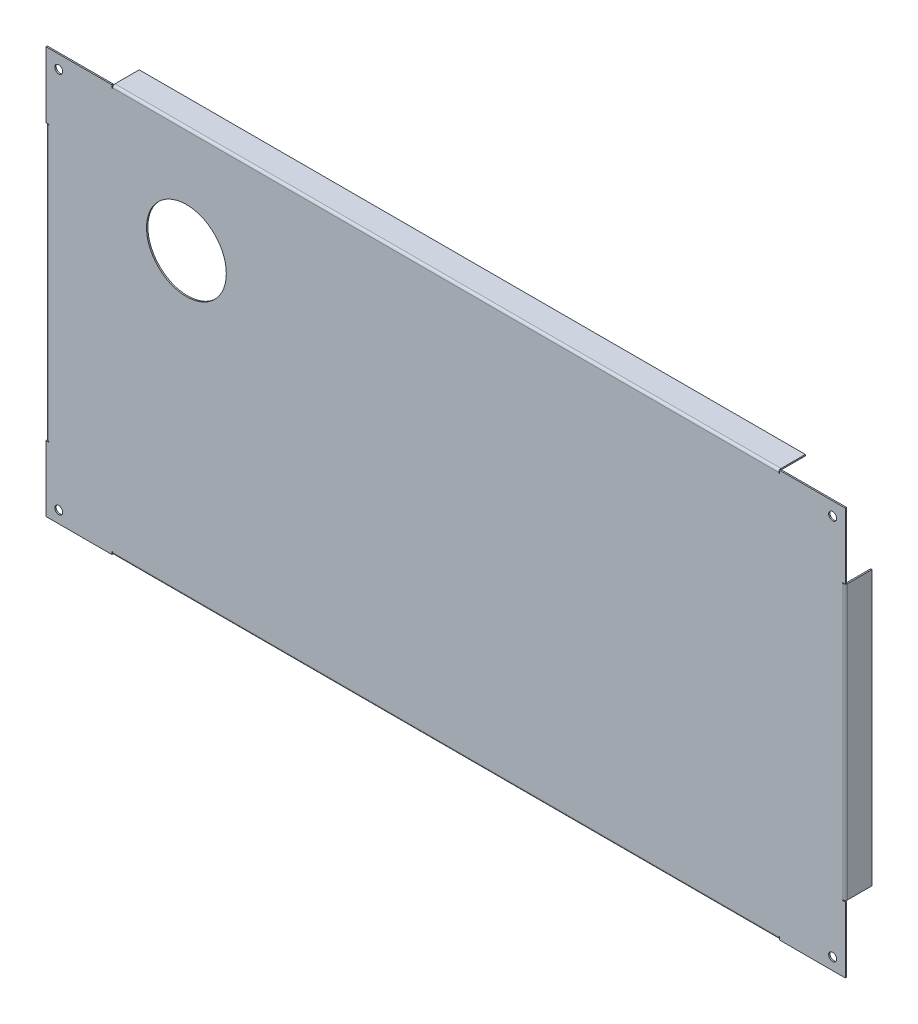
SolidWorks part; units mm, degrees
note: The reader was unsure of these and kept them because the rebuilt part matched: flange length of "边线-法兰1", "边线-法兰2", "边线-法兰3", "边线-法兰4".
ref_plane "前视基准面" through (0, 0, 0) normal (0, 0, 1) x (1, 0, 0)
ref_plane "上视基准面" through (0, 0, 0) normal (0, 1, 0) x (1, 0, 0)
ref_plane "右视基准面" through (0, 0, 0) normal (1, 0, 0) x (0, 0, -1)
sketch "草图1" plane through (0, 0, 0) normal (0, 0, 1) x (1, 0, 0)
  line L1 (-300.5, 153) -> (300.5, 153)
  line L2 (-300.5, 153) -> (-300.5, -153)
  line L3 (-300.5, -153) -> (300.5, -153)
  line L4 (300.5, 153) -> (300.5, -153)
  line L5 (-300.5, 153) -> (300.5, -153) construction
  line L6 (-300.5, -153) -> (300.5, 153) construction
  circle A0 centre (-195, 73) radius 30
  point P0 (0, 0)
  dimension "D3" = 60
  dimension "D1" = 601
  dimension "D2" = 306
  dimension "D4" = 80
  dimension "D5" = 105.5
sheet metal parameters "钣金1" thickness 1 parameters "D1"=0.7366
base flange "基体-法兰1" sketch "草图1" thickness 1 reverse thickness direction no parameters "D1"=0.7366
edge flange "边线-法兰1" sketch "草图5" flange angle 90 flange length 19 flange position material inside bend radius 0.7366 thickness 1 relief rectangular parameters "D6"=10
sketch "草图5" plane through (0, 153, -1) normal (0, 1, 0) x (1, 0, 0)
  line L0 (300.5, 0) -> (-300.5, 0) construction
  line L1 (250.5, 0) -> (-250.5, 0)
  line L2 (-250.5, 0) -> (-250.5, 19)
  line L3 (-250.5, 19) -> (250.5, 19)
  line L4 (250.5, 19) -> (250.5, 0)
  line L5 (300.5, -1) -> (-300.5, -1) construction
  line L6 (-300.5, 0) -> (-300.5, -1) construction
  line L7 (300.5, 0) -> (300.5, -1) construction
  dimension "D1" = 20
  dimension "D2" = 50
  dimension "D3" = 50
bend "边线折弯1" bend radius 0.7366 bend angle 90 parameters "D5"=1
edge flange "边线-法兰2" sketch "草图8" flange angle 90 flange length 19 flange position material inside bend radius 0.7366 thickness 1 relief rectangular parameters "D6"=10
sketch "草图8" plane through (300.5, 0, -1) normal (1, 0, 0) x (0, -1, 0)
  line L0 (153, 0) -> (-153, 0) construction
  line L1 (103, 0) -> (-103, 0)
  line L2 (-103, 0) -> (-103, 19)
  line L3 (-103, 19) -> (103, 19)
  line L4 (103, 19) -> (103, 0)
  line L5 (-153, 0) -> (-153, -1) construction
  line L6 (153, 0) -> (153, -1) construction
  line L7 (153, -1) -> (-153, -1) construction
  dimension "D1" = 50
  dimension "D2" = 20
  dimension "D3" = 50
bend "边线折弯2" bend radius 0.7366 bend angle 90 parameters "D5"=2
edge flange "边线-法兰3" sketch "草图11" flange angle 90 flange length 19 flange position material inside bend radius 0.7366 thickness 1 relief rectangular parameters "D6"=10
sketch "草图11" plane through (0, -153, -1) normal (0, -1, 0) x (-1, 0, 0)
  line L2 (-250.5, 0) -> (-250.5, 19)
  line L3 (-250.5, 19) -> (250.5, 19)
  line L4 (250.5, 19) -> (250.5, 0)
  line L7 (300.5, 0) -> (-300.5, 0) construction
  line L8 (250.5, 0) -> (-250.5, 0)
  line L9 (300.5, 0) -> (300.5, -1) construction
  line L10 (300.5, -1) -> (-300.5, -1) construction
  line L11 (-300.5, 0) -> (-300.5, -1) construction
  dimension "D1" = 50
  dimension "D2" = 20
  dimension "D3" = 50
bend "边线折弯3" bend radius 0.7366 bend angle 90 parameters "D5"=3
edge flange "边线-法兰4" sketch "草图14" flange angle 90 flange length 19 flange position material inside bend radius 0.7366 thickness 1 relief rectangular parameters "D6"=10
sketch "草图14" plane through (-300.5, 0, -1) normal (-1, 0, 0) x (0, 1, 0)
  line L2 (-103, 0) -> (-103, 19)
  line L3 (-103, 19) -> (103, 19)
  line L4 (103, 19) -> (103, 0)
  line L5 (153, 0) -> (-153, 0) construction
  line L6 (103, 0) -> (-103, 0)
  line L7 (153, -1) -> (-153, -1) construction
  line L8 (153, 0) -> (153, -1) construction
  line L9 (-153, 0) -> (-153, -1) construction
  dimension "D1" = 20
  dimension "D2" = 50
  dimension "D3" = 50
bend "边线折弯4" bend radius 0.7366 bend angle 90 parameters "D5"=4
sketch "草图15" plane through (0, 0, 0) normal (0, 0, 1) x (1, 0, 0)
  circle A0 centre (-291, -144) radius 3
  circle A1 centre (-291, 143) radius 3
  circle A2 centre (291, 143) radius 3
  circle A3 centre (291, -144) radius 3
  dimension "D1" = 6
extrude "切除-拉伸1" cut sketch "草图15" against normal through all normal cut yes
flat pattern "平板型式1" [suppressed]
sketch "折弯-线1" plane through (0, 0, 0) normal (0, 1, 0) x (-1, 0, 0)
bend of the flat pattern "展开-<边线折弯1>1"
bend of the flat pattern "展开-<边线折弯2>1"
bend of the flat pattern "展开-<边线折弯3>1"
bend of the flat pattern "展开-<边线折弯4>1"
